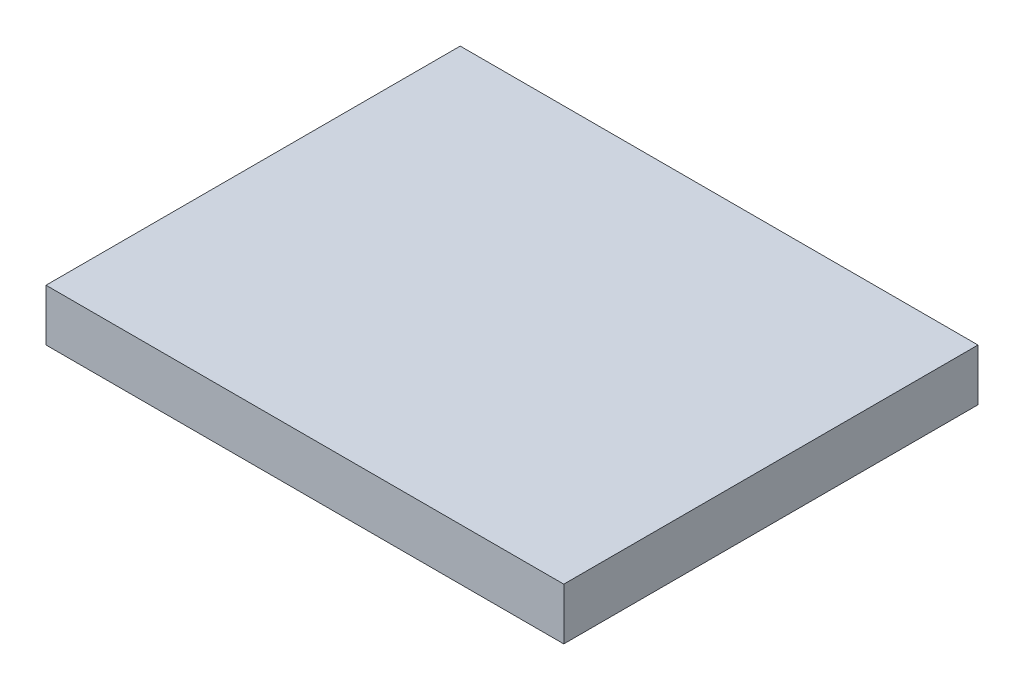
SolidWorks part; units mm, degrees
ref_plane "Front Plane" through (0, 0, 0) normal (0, 0, 1) x (1, 0, 0)
ref_plane "Top Plane" through (0, 0, 0) normal (0, 1, 0) x (1, 0, 0)
ref_plane "Right Plane" through (0, 0, 0) normal (1, 0, 0) x (0, 0, -1)
sketch "Sketch1" plane through (0, 0, 0) normal (0, 1, 0) x (1, 0, 0)
  line L1 (-25, 20) -> (25, 20)
  line L2 (-25, 20) -> (-25, -20)
  line L3 (-25, -20) -> (25, -20)
  line L4 (25, 20) -> (25, -20)
  line L5 (-25, 20) -> (25, -20) construction
  line L6 (-25, -20) -> (25, 20) construction
  point P0 (0, 0)
  dimension "D1" = 40
  dimension "D2" = 50
extrude "Boss-Extrude1" add sketch "Sketch1" along normal blind 5
